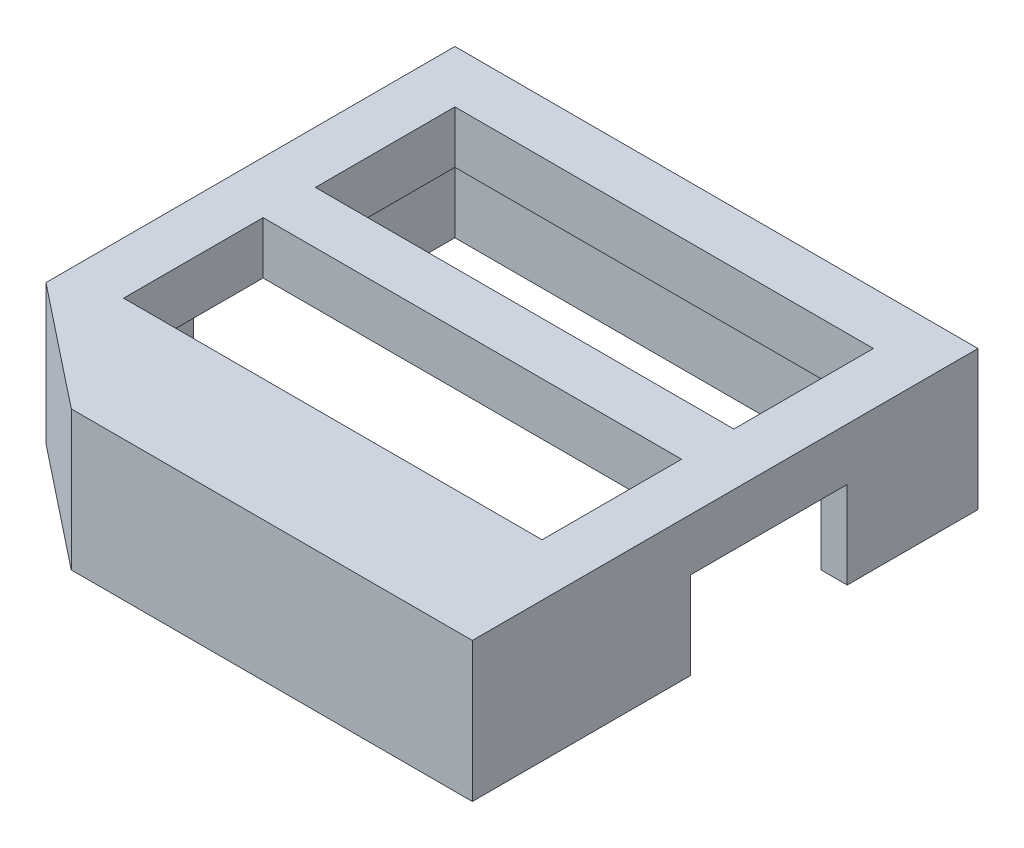
SolidWorks part; units mm, degrees
ref_plane "Front Plane" through (0, 0, 0) normal (0, 0, 1) x (1, 0, 0)
ref_plane "Top Plane" through (0, 0, 0) normal (0, 1, 0) x (1, 0, 0)
ref_plane "Right Plane" through (0, 0, 0) normal (1, 0, 0) x (0, 0, -1)
sketch "Sketch1" plane through (0, 0, 0) normal (0, 1, 0) x (1, 0, 0)
  line L1 (-29.2366, 0.9308) -> (0.7634, 0.9308)
  line L2 (-29.2366, 0.9308) -> (-29.2366, -28.0692)
  line L3 (-29.2366, -28.0692) -> (0.7634, -28.0692)
  line L4 (0.7634, 0.9308) -> (0.7634, -28.0692)
  dimension "D1" = 30
  dimension "D2" = 29
extrude "Boss-Extrude1" add sketch "Sketch1" along normal blind 8
sketch "Sketch2" plane through (0, 8, 0) normal (0, 1, 0) x (1, 0, 0)
  line L0 (-29.2366, 0.9308) -> (-29.2366, -28.0692) construction
  line L1 (-26.2366, -2.0692) -> (-2.2366, -2.0692)
  line L2 (-26.2366, -2.0692) -> (-26.2366, -10.0692)
  line L3 (-26.2366, -10.0692) -> (-2.2366, -10.0692)
  line L4 (-2.2366, -2.0692) -> (-2.2366, -10.0692)
  line L5 (-26.2366, -13.0692) -> (-2.2366, -13.0692)
  line L6 (-26.2366, -13.0692) -> (-26.2366, -21.0692)
  line L7 (-26.2366, -21.0692) -> (-2.2366, -21.0692)
  line L8 (-2.2366, -13.0692) -> (-2.2366, -21.0692)
  line L9 (0.7634, -28.0692) -> (0.7634, 0.9308) construction
  line L10 (0.7634, 0.9308) -> (-29.2366, 0.9308) construction
  dimension "D1" = 3
  dimension "D2" = 3
  dimension "D3" = 3
  dimension "D4" = 3
  dimension "D5" = 8
  dimension "D6" = 3
extrude "Cut-Extrude1" cut sketch "Sketch2" against normal blind 8
sketch "Sketch3" plane through (0, 8, 0) normal (0, 1, 0) x (1, 0, 0)
  line L0 (-29.2366, -22.5191) -> (-22.2366, -28.0692)
  line L1 (-29.2366, 0.9308) -> (-29.2366, -28.0692) construction
  line L2 (-29.2366, -28.0692) -> (0.7634, -28.0692) construction
  line L3 (-22.2366, -28.0692) -> (-29.2366, -28.0692)
  line L4 (-29.2366, -28.0692) -> (-29.2366, -22.5191)
  dimension "D1" = 3
  dimension "D2" = 7
extrude "Cut-Extrude2" cut sketch "Sketch3" against normal blind 8
sketch "Sketch4" plane through (0, 0, 0) normal (0, -1, 0) x (1, 0, 0)
  line L0 (-0.7366, 0.5692) -> (-27.7366, 0.5692)
  line L1 (-27.7366, 0.5692) -> (-27.7366, 21.7942)
  line L2 (-27.7366, 21.7942) -> (-21.7141, 26.5692)
  line L3 (-21.7141, 26.5692) -> (-0.7366, 26.5692)
  line L4 (-0.7366, 0.5692) -> (-0.7366, 26.5692)
  line L5 (0.7634, 28.0692) -> (0.7634, -0.9308) construction
  line L6 (-22.2366, 28.0692) -> (0.7634, 28.0692) construction
  line L7 (-22.2366, 28.0692) -> (-29.2366, 22.5191) construction
  line L8 (-29.2366, -0.9308) -> (-29.2366, 22.5191) construction
  line L9 (0.7634, -0.9308) -> (-29.2366, -0.9308) construction
  point P15 (-25.7366, 25.2942)
  dimension "D1" = 1.5
  dimension "D2" = 1.5
  dimension "D3" = 1.5
  dimension "D4" = 1.5
  dimension "D5" = 1.5
extrude "Cut-Extrude3" cut sketch "Sketch4" against normal blind 5
sketch "Sketch5" plane through (-29.2366, 0, 0) normal (-1, 0, 0) x (0, 0, 1)
  line L0 (-0.9308, 0) -> (22.5191, 0) construction
  line L1 (6.5692, 0) -> (15.5692, 0)
  line L2 (6.5692, 0) -> (6.5692, 5)
  line L3 (6.5692, 5) -> (15.5692, 5)
  line L4 (15.5692, 0) -> (15.5692, 5)
  line L5 (-0.9308, 8) -> (-0.9308, 0) construction
  dimension "D1" = 9
  dimension "D2" = 5
  dimension "D3" = 7.5
extrude "Cut-Extrude4" cut sketch "Sketch5" against normal blind 30
